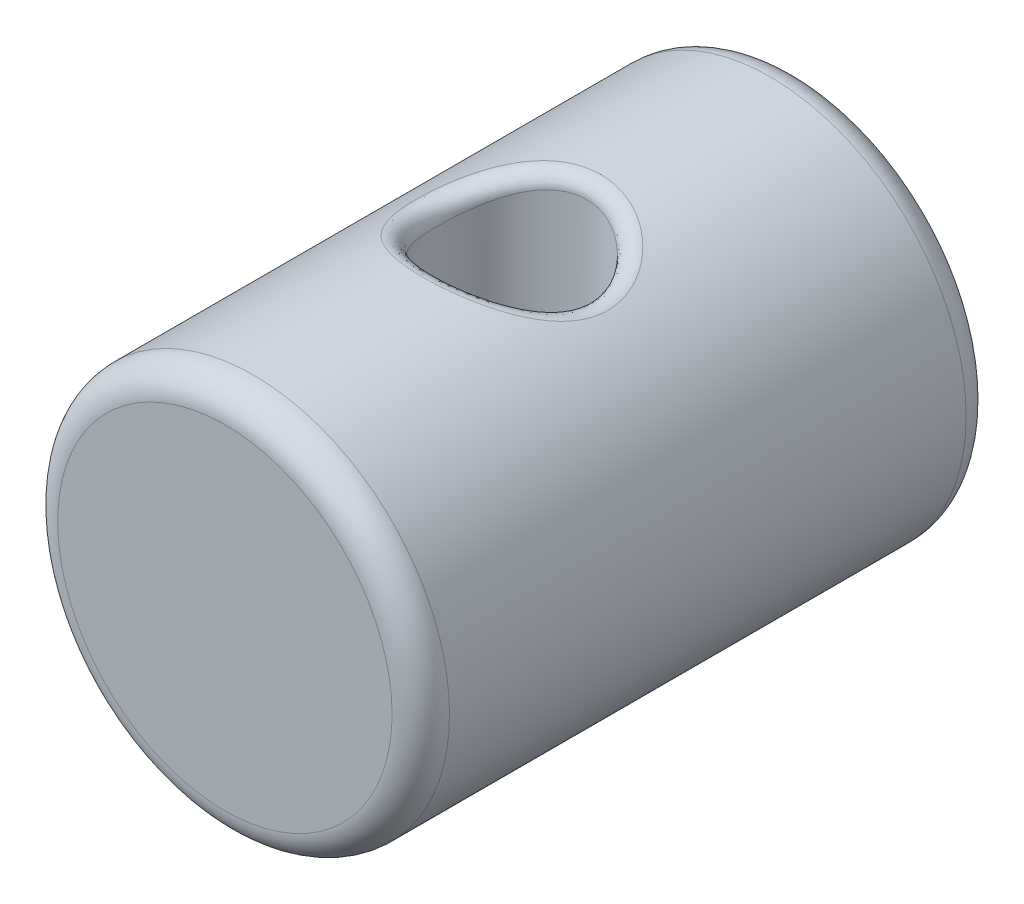
SolidWorks part; units mm, degrees
ref_plane "Front Plane" through (0, 0, 0) normal (0, 0, 1) x (1, 0, 0)
ref_plane "Top Plane" through (0, 0, 0) normal (0, 1, 0) x (1, 0, 0)
ref_plane "Right Plane" through (0, 0, 0) normal (1, 0, 0) x (0, 0, -1)
sketch "Sketch1" plane through (0, 0, 0) normal (0, 0, 1) x (1, 0, 0)
  circle A0 centre (0, 0) radius 6.825
  dimension "D1" = 13.65
extrude "Boss-Extrude1" add sketch "Sketch1" along normal blind 10 and the other way blind 10
sketch "Sketch2" plane through (0, 0, 0) normal (0, 1, 0) x (1, 0, 0)
  circle A0 centre (0, 0) radius 2.6
  dimension "D1" = 5.2
extrude "Cut-Extrude1" cut sketch "Sketch2" against normal through all and the other way through all
fillet "Fillet1" radius 1 2 edges at (6.825, 0, -10) (6.825, 0, 10)
fillet "Fillet2" radius 0.5 2 edges at (0.3965, -6.8135, -2.5696) (-0.3965, 6.8135, -2.5696)
